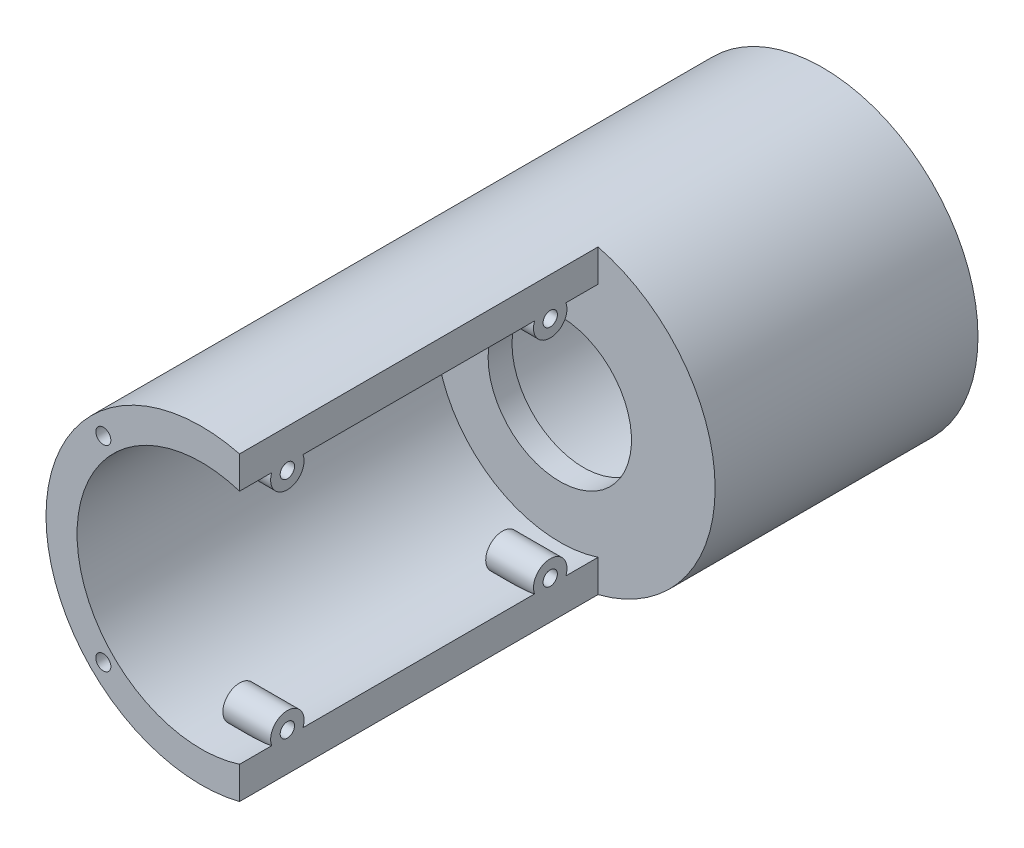
SolidWorks part; units mm, degrees
ref_plane "Спереди" through (0, 0, 0) normal (0, 0, 1) x (1, 0, 0)
ref_plane "Сверху" through (0, 0, 0) normal (0, 1, 0) x (1, 0, 0)
ref_plane "Справа" through (0, 0, 0) normal (1, 0, 0) x (0, 0, -1)
sketch "Эскиз1" plane through (0, 0, 0) normal (0, 0, 1) x (1, 0, 0)
  circle A1 centre (0, 0) radius 32.5
  dimension "D1" = 65
extrude "Бобышка-Вытянуть1" add sketch "Эскиз1" along normal blind 130
sketch "Эскиз3" plane through (0, 0, 0) normal (0, 0, -1) x (-1, 0, 0)
  circle A0 centre (0, 0) radius 22.5
  dimension "D1" = 45
extrude "Вырез-Вытянуть1" cut sketch "Эскиз3" against normal blind 50 contours A0
sketch "Эскиз4" plane through (0, 0, 130) normal (0, 0, 1) x (1, 0, 0)
  circle A0 centre (0, 0) radius 26
  dimension "D1" = 52
extrude "Вырез-Вытянуть2" cut sketch "Эскиз4" against normal offset from surface (75 mm away) 5 up to face at (-22.5, 0, 50)
sketch "Эскиз6" plane through (0, 0, 130) normal (0, 0, 1) x (1, 0, 0)
  line L2 (0, 32.5) -> (0, -32.5) construction
  line L4 (0, 0) -> (9.8537, 38.7989) construction
  line L5 (0, 0) -> (60.0556, 0) construction
  line L6 (0, 0) -> (13.3732, -52.657) construction
  line L7 (8, 31.5) -> (8, -31.5)
  circle A0 centre (0, 0) radius 32.5 construction
  circle A2 centre (0, 0) radius 32.5 construction
  circle A3 centre (0, 0) radius 32.5 construction
  arc A4 (8, -31.5) -> (8, 31.5) centre (0, 0) ccw
  dimension "D1" = 75.75
  dimension "D2" = 75.75
extrude "Вырез-Вытянуть4" cut sketch "Эскиз6" against normal offset from surface (75 mm away) 5 up to face at (-22.5, 0, 50)
sketch "Эскиз10" plane through (0, 0, 50) normal (0, 0, -1) x (-1, 0, 0)
  circle A0 centre (0, 0) radius 15
  dimension "D1" = 30
extrude "Вырез-Вытянуть5" cut sketch "Эскиз10" against normal blind 5
hole_wizard "Сверло под метчик  спиральное M31" positions "Трехмерный эскиз1" profile "Эскиз11" hole size "M3x0.5" standard "Ansi Metric"
sketch3d "Трехмерный эскиз1"
  line L0 (0, 0, 130) -> (0, 0, 55) construction
  line L1 (0, 0, 130) -> (-32.8656, 0, 130) construction
  line L2 (0, 0, 130) -> (-20.5061, -20.5061, 130) construction
  circle A0 centre (0, 0, 130) radius 29
  point P8 (0, 0, 159)
  point P18 (-20.5061, -20.5061, 130)
  dimension "D1" = 29
  dimension "D2" = 45
sketch "Эскиз11" plane through (-20.5061, -20.5061, 130) normal (1, 0, 0) x (0, -1, 0)
  line L0 (0, 0) -> (0, 7.9464)
  line L1 (0, 7.9464) -> (1.575, 7)
  line L2 (1.575, 7) -> (1.575, 0)
  line L5 (1.575, 0) -> (0, 0)
  line L10 (0, 7.9464) -> (-1.575, 7) construction
  line L11 (0, -6.35) -> (0, 107.95) construction
  dimension "Диаметр отверстия" = 3.15
  dimension "Глубина отверстия" = 7
  dimension "Угол заточки сверла" = 118
pattern_circular "Круговой массив1" count 2 every 90 about axis through (0, 0, 130) along (0, 0, -1) of "Сверло под метчик  спиральное M31"
sketch "Эскиз12" plane through (8, 0, 0) normal (1, 0, 0) x (0, 0, -1)
  line L0 (-55, 31.5) -> (-55, 24.7386) construction
  line L1 (-55, 31.5) -> (-130, 31.5) construction
  line L2 (-92.5, 24.7386) -> (-92.5, -24.7386) construction
  line L3 (-55, 24.7386) -> (-130, 24.7386) construction
  line L4 (-130, -24.7386) -> (-55, -24.7386) construction
  line L5 (-130, 0) -> (-16.2463, 0) construction
  line L6 (-130, 26) -> (-130, -26) construction
  line L7 (-130, 0) -> (-55, 0) construction
  line L8 (-50, 0) -> (0, 0) construction
  circle A0 centre (-65, 23.5) radius 3.5
  circle A1 centre (-120, 23.5) radius 3.5
  circle A2 centre (-65, -23.5) radius 3.5
  circle A3 centre (-120, -23.5) radius 3.5
  dimension "D1" = 7
  dimension "D2" = 10
  dimension "D3" = 8
extrude "Бобышка-Вытянуть4" add sketch "Эскиз12" against normal blind 10 from surface starting at face at (8, -28.1193, 92.5)
sketch "Эскиз13" plane through (8, 0, 0) normal (1, 0, 0) x (0, 0, -1)
  line L0 (-92.5, 24.7386) -> (-92.5, -24.7386) construction
  line L1 (-68.2735, 24.7386) -> (-116.7265, 24.7386) construction
  line L2 (-116.7265, -24.7386) -> (-68.2735, -24.7386) construction
  line L3 (-130, 0) -> (-26.2102, 0) construction
  line L4 (-130, 26) -> (-130, -26) construction
  line L5 (-50, 0) -> (0, 0) construction
  line L6 (-55, 0) -> (-130, 0) construction
  circle A0 centre (-120, 23.5) radius 1.5
  circle A1 centre (-65, 23.5) radius 1.5
  circle A2 centre (-65, -23.5) radius 1.5
  circle A3 centre (-120, -23.5) radius 1.5
  dimension "D1" = 3
extrude "Вырез-Вытянуть6" cut sketch "Эскиз13" against normal blind 7
chamfer "Фаска1" distance 1 angle 45 1 edges at (-22.5, 0, 0)
